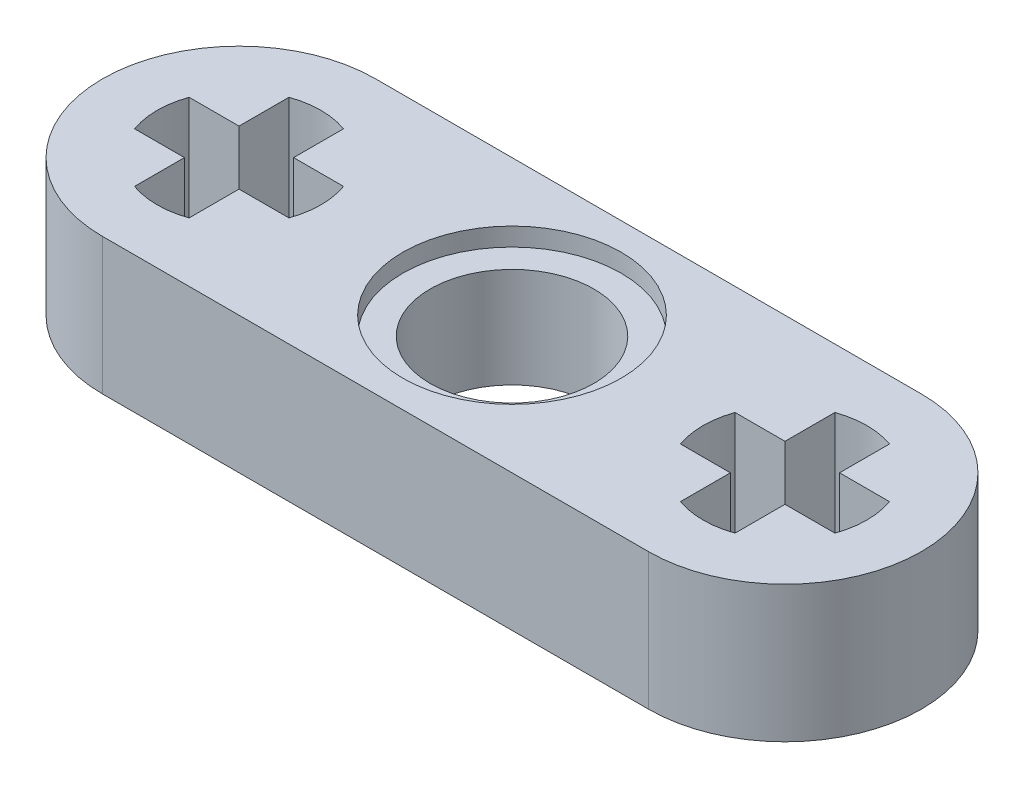
SolidWorks part; units mm, degrees
ref_plane "Front Plane" through (0, 0, 0) normal (0, 0, 1) x (1, 0, 0)
ref_plane "Top Plane" through (0, 0, 0) normal (0, 1, 0) x (1, 0, 0)
ref_plane "Right Plane" through (0, 0, 0) normal (1, 0, 0) x (0, 0, -1)
sketch "Sketch1" plane through (0, 0, 0) normal (0, 1, 0) x (1, 0, 0)
  line L0 (3.5, 0.5) -> (6.5, 0.5)
  line L1 (-7.5, -2.5) -> (7.5, -2.5)
  line L2 (-7.5, -2.5) -> (-7.5, 2.5)
  line L3 (-7.5, 2.5) -> (7.5, 2.5)
  line L4 (7.5, -2.5) -> (7.5, 2.5)
  line L5 (-7.5, -2.5) -> (7.5, 2.5) construction
  line L6 (-7.5, 2.5) -> (7.5, -2.5) construction
  line L7 (-4.5, -1.5) -> (-5.5, -1.5)
  line L8 (-4.5, -1.5) -> (-4.5, 1.5)
  line L9 (-4.5, 1.5) -> (-5.5, 1.5)
  line L10 (-5.5, -1.5) -> (-5.5, 1.5)
  line L11 (-4.5, -1.5) -> (-5.5, 1.5) construction
  line L12 (-4.5, 1.5) -> (-5.5, -1.5) construction
  line L13 (-6.5, -0.5) -> (-3.5, -0.5)
  line L14 (-6.5, -0.5) -> (-6.5, 0.5)
  line L15 (-6.5, 0.5) -> (-3.5, 0.5)
  line L16 (-3.5, -0.5) -> (-3.5, 0.5)
  line L17 (-6.5, -0.5) -> (-3.5, 0.5) construction
  line L18 (-6.5, 0.5) -> (-3.5, -0.5) construction
  line L19 (4.5, -1.5) -> (4.5, 1.5)
  line L20 (5.5, -1.5) -> (5.5, 1.5)
  line L21 (3.5, -0.5) -> (6.5, -0.5)
  circle A0 centre (0, 0) radius 2.5
  circle A1 centre (0, 0) radius 2
  circle A2 centre (0, 0) radius 1.5
  circle A3 centre (-5, 0) radius 1.5
  circle A4 centre (5, 0) radius 1.5
  circle A5 centre (-5, 0) radius 2.5
  circle A6 centre (5, 0) radius 2.5
  point P0 (0, 0)
  point P13 (-7.5, 0)
  dimension "D3" = 3
  dimension "D4" = 4
  dimension "D5" = 3
  dimension "D1" = 5
  dimension "D2" = 15
  dimension "D6" = 2.5
  dimension "D7" = 1
  dimension "D8" = 3
  dimension "D9" = 2
extrude "Boss-Extrude1" add sketch "Sketch1" along normal blind 1.25 contours A5 A3 L8 L7 L10 L13 L14 L15 L9 L16 | A3 L9 L10 | A3 L8 L9 | A3 L15 L14 | A3 L14 L13 | A3 L10 L7 | A3 L7 L8 | A3 L13 L16 | A3 L16 L15 | L15 A3 L8 | L13 A3 L10 | L10 A3 L15 | L8 A3 L13 | A5 A0 L3 | A5 L1 A0 | A0 A1 | A1 A2 | A6 L3 A0 | A6 A0 L1 | A6 A4 | L19 A4 L0 | L0 A4 L20 | L20 A4 L21 | L21 A4 L19 region at (4.1499, 0, -0.8501) region at (4.1499, 0, 0.8501) region at (5.8501, 0, -0.8501) region at (5.8501, 0, 0.8501) region at (-2.5, 0, 1.9416) region at (-6.7178, 0, 1.7178) region at (2.5, 0, 1.9416) region at (-1.7178, 0, 1.7178) region at (-2.5, 0, -1.9416) region at (3.2822, 0, 1.7178) region at (2.5, 0, -1.9416) region at (-4.6243, 0, 1.4744) region at (-5.3757, 0, 1.4744) region at (-4.1499, 0, 0.8501) region at (-5.8501, 0, 0.8501) region at (-3.5256, 0, 0.3757) region at (-6.4744, 0, 0.3757) region at (-4.1499, 0, -0.8501) region at (-3.5256, 0, -0.3757) region at (-5.8501, 0, -0.8501) region at (-6.4744, 0, -0.3757) region at (-4.6243, 0, -1.4744) region at (-5.3757, 0, -1.4744) region at (-1.9434, 0, 0)
extrude "Cut-Extrude1" cut sketch "Sketch1<3>" along normal blind 0.3333 contours A1 A2 region at (-1.9434, 0, 0)
sketch "Sketch1<3>" plane through (0, 0, 0) normal (0, 1, 0) x (1, 0, 0) same geometry as "Sketch1"
mirror "Mirror1" about plane through (0, 1.25, 0) normal (0, 1, 0) of "Boss-Extrude1", "Cut-Extrude1"
